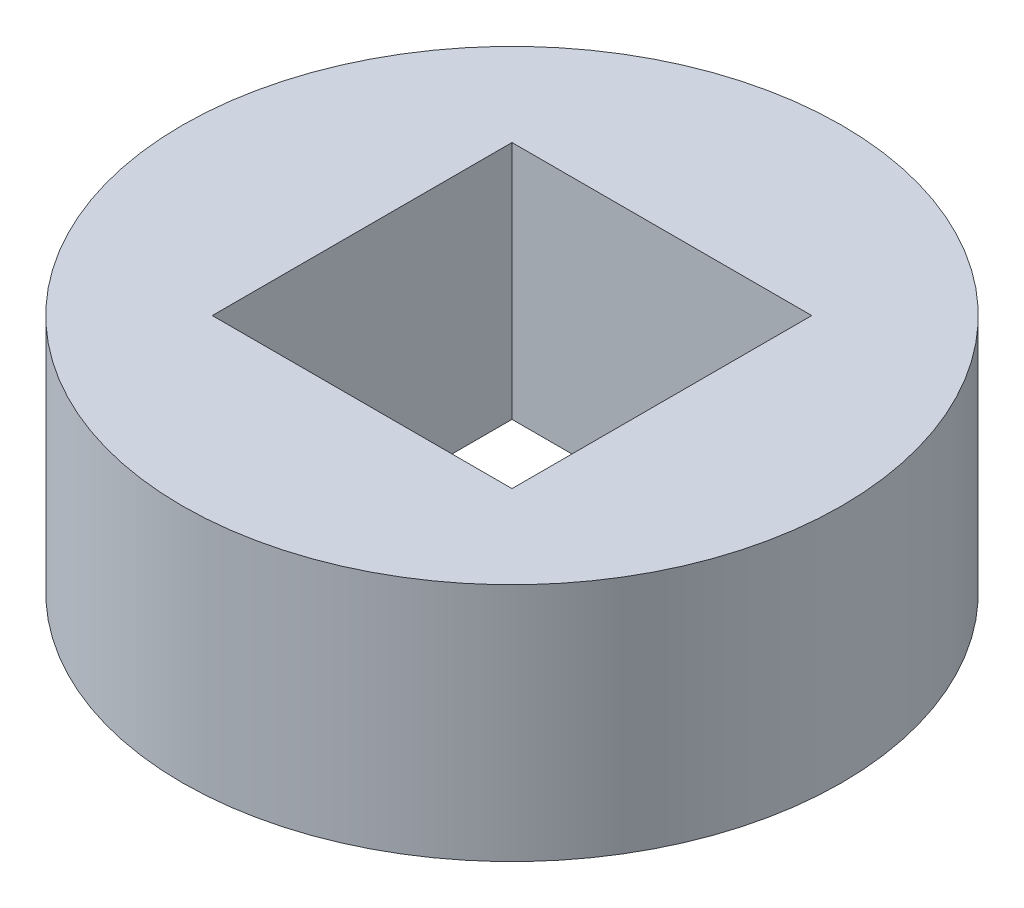
SolidWorks part; units mm, degrees
ref_plane "Front Plane" through (0, 0, 0) normal (0, 0, 1) x (1, 0, 0)
ref_plane "Top Plane" through (0, 0, 0) normal (0, 1, 0) x (1, 0, 0)
ref_plane "Right Plane" through (0, 0, 0) normal (1, 0, 0) x (0, 0, -1)
sketch "Sketch1" plane through (0, 0, 0) normal (0, 1, 0) x (1, 0, 0)
  line L1 (-12.5, -12.5) -> (12.5, -12.5)
  line L2 (-12.5, -12.5) -> (-12.5, 12.5)
  line L3 (-12.5, 12.5) -> (12.5, 12.5)
  line L4 (12.5, -12.5) -> (12.5, 12.5)
  line L5 (-12.5, -12.5) -> (12.5, 12.5) construction
  line L6 (-12.5, 12.5) -> (12.5, -12.5) construction
  circle A1 centre (0, 0) radius 27.5
  dimension "D1" = 25
  dimension "D2" = 55
  dimension "D3" = 25
extrude "Boss-Extrude1" add sketch "Sketch1" along normal blind 20
